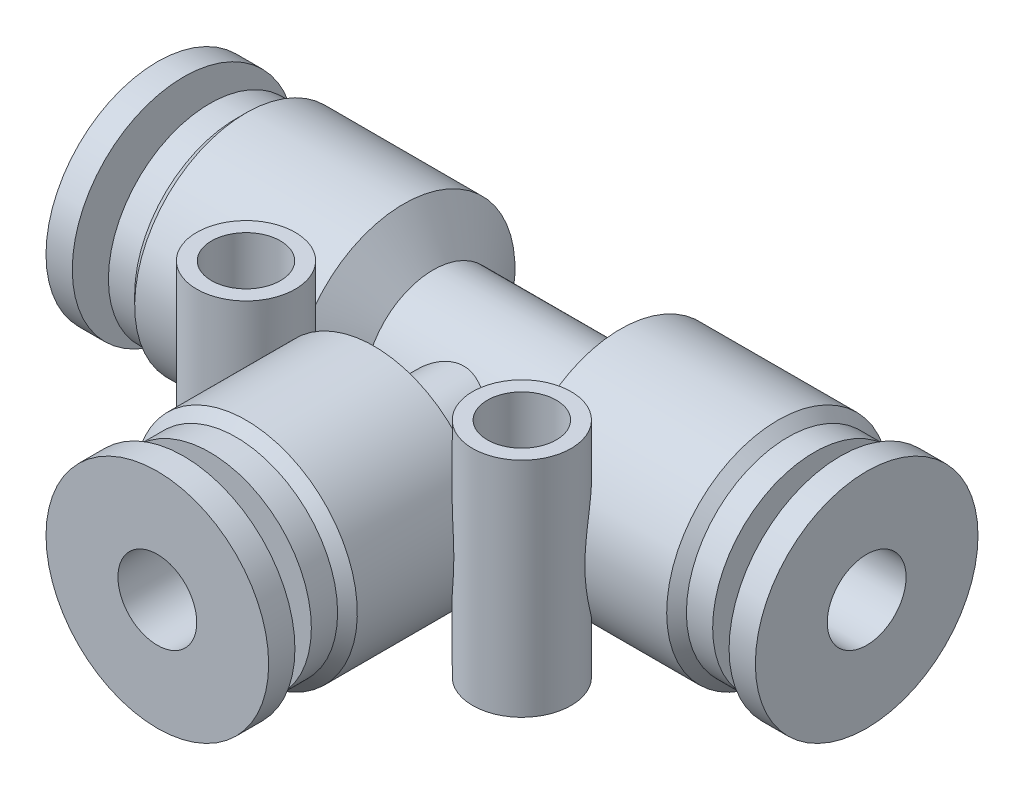
SolidWorks part; units mm, degrees
ref_plane "Front Plane" through (0, 0, 0) normal (0, 0, 1) x (1, 0, 0)
ref_plane "Top Plane" through (0, 0, 0) normal (0, 1, 0) x (1, 0, 0)
ref_plane "Right Plane" through (0, 0, 0) normal (1, 0, 0) x (0, 0, -1)
sketch "Sketch4" plane through (0, 0, 0) normal (0, 1, 0) x (1, 0, 0)
  line L0 (-7, -0.15) -> (7, -0.15) construction
  line L1 (-18.25, 12) -> (18.25, 12) construction
  line L2 (-18.25, 12) -> (-18.25, -12) construction
  line L3 (-18.25, -12) -> (18.25, -12) construction
  line L4 (18.25, 12) -> (18.25, -12) construction
  line L5 (-18.25, 12) -> (18.25, -12) construction
  line L6 (-18.25, -12) -> (18.25, 12) construction
  line L7 (-14, 6.35) -> (14, 6.35) construction
  line L8 (14, 12) -> (5.5, 12) construction
  line L9 (14, 12) -> (14, 0.7) construction
  line L10 (14, 0.7) -> (5.5, 0.7) construction
  line L11 (5.5, 12) -> (5.5, 0.7) construction
  line L12 (5.5, 9.85) -> (-5.5, 9.85) construction
  line L13 (5.5, 9.85) -> (5.5, 2.85) construction
  line L14 (5.5, 2.85) -> (-5.5, 2.85) construction
  line L15 (-5.5, 9.85) -> (-5.5, 2.85) construction
  line L16 (-14, 12) -> (-5.5, 12) construction
  line L17 (-14, 12) -> (-14, 0.7) construction
  line L18 (-14, 0.7) -> (-5.5, 0.7) construction
  line L19 (-5.5, 12) -> (-5.5, 0.7) construction
  line L20 (-2.5, 2.85) -> (2.5, 2.85) construction
  line L21 (-2.5, 2.85) -> (-2.5, 0.85) construction
  line L22 (-2.5, 0.85) -> (2.5, 0.85) construction
  line L23 (2.5, 2.85) -> (2.5, 0.85) construction
  line L24 (-5.65, 0.85) -> (5.65, 0.85) construction
  line L25 (-5.65, 0.85) -> (-5.65, -7.65) construction
  line L26 (-5.65, -7.65) -> (5.65, -7.65) construction
  line L27 (5.65, 0.85) -> (5.65, -7.65) construction
  line L28 (-14, 6.35) -> (-14, 12)
  line L29 (-14, 12) -> (-5.5, 12)
  line L30 (-5.5, 12) -> (-4, 9.85)
  line L31 (-4, 9.85) -> (4, 9.85)
  line L32 (4, 9.85) -> (5.5, 12)
  line L33 (5.5, 12) -> (14, 12)
  line L34 (14, 12) -> (14, 6.35)
  line L35 (-14, 6.35) -> (14, 6.35)
  circle A0 centre (7, -0.15) radius 1.75 construction
  circle A1 centre (-7, -0.15) radius 1.75 construction
  circle A2 centre (7, -0.15) radius 2.5 construction
  circle A3 centre (-7, -0.15) radius 2.5 construction
  point P0 (0, 0)
  point P10 (0, -0.15)
  point P25 (0, 2.85)
  point P27 (5.5, 6.35)
  point P28 (5.5, 6.35)
  point P36 (0, 0.85)
  point P37 (0, -7.65)
  point P42 (0, 9.85)
  dimension "D4" = 3.5
  dimension "D5" = 5
  dimension "D1" = 36.5
  dimension "D2" = 24
  dimension "D3" = 14
  dimension "D6" = 6.5
  dimension "D7" = 8.5
  dimension "D8" = 11
  dimension "D9" = 7
  dimension "D10" = 11.3
  dimension "D11" = 2
  dimension "D12" = 1.5
  dimension "D13" = 5
revolve "Revolve1" add sketch "Sketch4" angle 360 about L35
sketch "Sketch5" plane through (0, 0, 0) normal (0, 1, 0) x (1, 0, 0)
  line L0 (5.65, 0.85) -> (5.65, -7.65) construction
  line L1 (5.65, 0.85) -> (5.65, -7.65) construction
  line L3 (-2.5, 2.85) -> (-2.5, 0.85) construction
  line L4 (-5.65, 0.85) -> (5.65, 0.85) construction
  line L5 (-5.65, 0.85) -> (-5.65, -7.65) construction
  line L6 (-5.65, -7.65) -> (5.65, -7.65) construction
  line L8 (-2.5, 2.85) -> (-2.5, 0.85)
  line L9 (-5.65, 0.85) -> (5.65, 0.85) construction
  line L10 (-5.65, 0.85) -> (-5.65, -7.65) construction
  line L11 (-5.65, -7.65) -> (5.65, -7.65) construction
  line L12 (-2.5, 0.85) -> (-5.65, -0.65)
  line L13 (-5.65, -0.65) -> (-5.65, -7.65)
  line L14 (0, -7.65) -> (0, 6.35)
  line L17 (-5.65, -7.65) -> (0, -7.65)
  line L18 (-4, 2.85) -> (-4, 9.85) construction
  line L19 (-4, 2.85) -> (-4, 9.85) construction
  line L20 (-2.5, 2.85) -> (-2.5, 6.35)
  line L21 (-2.5, 6.35) -> (0, 6.35)
  point P16 (-4, 6.35)
  dimension "D1" = 1.5
revolve "Revolve2" add sketch "Sketch5" angle 360 about L14
sketch "Sketch6" plane through (0, 0, 0) normal (0, 1, 0) x (1, 0, 0)
  circle A0 centre (-7, -0.15) radius 2.5 construction
  circle A1 centre (7, -0.15) radius 2.5 construction
  circle A2 centre (-7, -0.15) radius 2.5
  circle A3 centre (7, -0.15) radius 2.5
extrude "Boss-Extrude1" add sketch "Sketch6" along normal blind 5.65 and the other way blind 5.65
sketch "Sketch7" plane through (0, 5.65, 0) normal (0, 1, 0) x (1, 0, 0)
  circle A0 centre (7, -0.15) radius 1.75 construction
  circle A1 centre (-7, -0.15) radius 1.75 construction
  circle A2 centre (7, -0.15) radius 1.75
  circle A3 centre (-7, -0.15) radius 1.75
extrude "Cut-Extrude1" cut sketch "Sketch7" against normal through all
sketch "Sketch8" plane through (0, 0, 0) normal (0, 1, 0) x (1, 0, 0)
  line L1 (-5.15, 4.5) -> (5.15, 4.5)
  line L2 (-5.15, 4.5) -> (-5.15, -0.5)
  line L3 (-5.15, -0.5) -> (5.15, -0.5)
  line L4 (5.15, 4.5) -> (5.15, -0.5)
  point P4 (0, 4.5)
  dimension "D1" = 0.5
  dimension "D2" = 10.3
  dimension "D3" = 5
extrude "Boss-Extrude3" add sketch "Sketch8" along normal blind 1 and the other way blind 1
chamfer "Chamfer1" distance 0.5 angle 45 3 edges at (5.65, 0, 7.65) (-14, 0, -0.7) (14, 0, -0.7)
sketch "Sketch9" plane through (14, 0, 0) normal (1, 0, 0) x (0, 0, -1)
  circle A1 centre (6.35, 0) radius 5.15
  circle A3 centre (6.35, 0) radius 5.15
  dimension "D1" = 0
extrude "Boss-Extrude4" add sketch "Sketch9" along normal blind 1.3333
sketch "Sketch10" plane through (-14, 0, 0) normal (-1, 0, 0) x (0, 0, 1)
  circle A1 centre (-6.35, 0) radius 5.15
  circle A3 centre (-6.35, 0) radius 5.15
  dimension "D1" = 0
extrude "Boss-Extrude5" add sketch "Sketch10" along normal blind 1.3333
sketch "Sketch11" plane through (0, 0, 7.65) normal (0, 0, 1) x (1, 0, 0)
  circle A1 centre (0, 0) radius 5.15
  circle A3 centre (0, 0) radius 5.15
  dimension "D1" = 0
extrude "Boss-Extrude6" add sketch "Sketch11" along normal blind 1.333
sketch "Sketch12" plane through (0, 0, 0) normal (0, 1, 0) x (1, 0, 0)
  line L0 (15.3333, 6.35) -> (18, 6.35)
  line L1 (15.3333, 1.2) -> (15.3333, 11.5) construction
  line L2 (18, 6.35) -> (18, 12)
  line L3 (18, 12) -> (16.6666, 12)
  line L4 (16.6666, 12) -> (16.6666, 9.35)
  line L5 (16.6666, 9.35) -> (15.3333, 9.35)
  line L6 (15.3333, 9.35) -> (15.3333, 6.35)
  line L7 (13.5, 12) -> (5.5, 12) construction
  line L8 (0, -1000) -> (0, 49000) construction
  line L9 (2.2913, 0.85) -> (-2.2913, 0.85) construction
  line L10 (-16.6666, 9.35) -> (-15.3333, 9.35)
  line L11 (-16.6666, 12) -> (-16.6666, 9.35)
  line L12 (-18, 12) -> (-16.6666, 12)
  line L13 (-18, 6.35) -> (-18, 12)
  line L14 (-15.3333, 6.35) -> (-18, 6.35)
  line L15 (-15.3333, 9.35) -> (-15.3333, 6.35)
  point P15 (0, 0.85)
  point P21 (18.2089, 6.35)
  dimension "D1" = 3
  dimension "D2" = 1.3333
revolve "Revolve3" add sketch "Sketch12" angle 360 about L14
sketch "Sketch13" plane through (0, 0, 0) normal (0, 1, 0) x (1, 0, 0)
  line L0 (-18, 12) -> (-16.6666, 12) construction
  line L1 (-16.6666, 12) -> (-16.6666, 9.35) construction
  line L2 (-16.6666, 9.35) -> (-15.3333, 9.35) construction
  line L3 (-15.3333, 9.35) -> (-15.3333, 6.35) construction
  line L4 (-15.3333, 6.35) -> (-18, 6.35) construction
  line L5 (-18, 6.35) -> (-18, 12) construction
  line L6 (-18, 12) -> (-16.6666, 12) construction
  line L7 (-16.6666, 12) -> (-16.6666, 9.35) construction
  line L8 (-16.6666, 9.35) -> (-15.3333, 9.35) construction
  line L9 (-15.3333, 9.35) -> (-15.3333, 6.35) construction
  line L10 (-15.3333, 6.35) -> (-18, 6.35) construction
  line L11 (-18, 6.35) -> (-18, 12) construction
  line L12 (0, -8.983) -> (0, -11.6497)
  line L13 (-5.15, -8.983) -> (5.15, -8.983) construction
  line L14 (0, -11.6497) -> (-5.65, -11.6497)
  line L15 (-5.65, -11.6497) -> (-5.65, -10.3163)
  line L16 (-5.65, -10.3163) -> (-3, -10.3163)
  line L17 (-3, -10.3163) -> (-3, -8.983)
  line L18 (-3, -8.983) -> (0, -8.983)
revolve "Revolve4" add sketch "Sketch13" angle 360 about L12
sketch "Sketch14" plane through (18, 0, 0) normal (1, 0, 0) x (0, 0, -1)
  circle A0 centre (6.35, 0) radius 2
  circle A1 centre (6.35, 0) radius 5.65
  circle A2 centre (6.35, 0) radius 5.65 construction
  dimension "D2" = 4
  dimension "D1" = 0
extrude "Cut-Extrude2" cut sketch "Sketch14" against normal through all
sketch "Sketch15" plane through (0, 0, 0) normal (0, 1, 0) x (1, 0, 0)
  line L0 (-18, 8.35) -> (-18, 4.35)
  point P4 (-18, 6.35)
sketch "Sketch16" plane through (0, 0, 11.6497) normal (0, 0, 1) x (1, 0, 0)
  circle A0 centre (0, 0) radius 2
  dimension "D1" = 4
extrude "Cut-Extrude3" cut sketch "Sketch16" against normal up to vertex (17.9997 mm away) up to point (-18, 0, -6.35)
